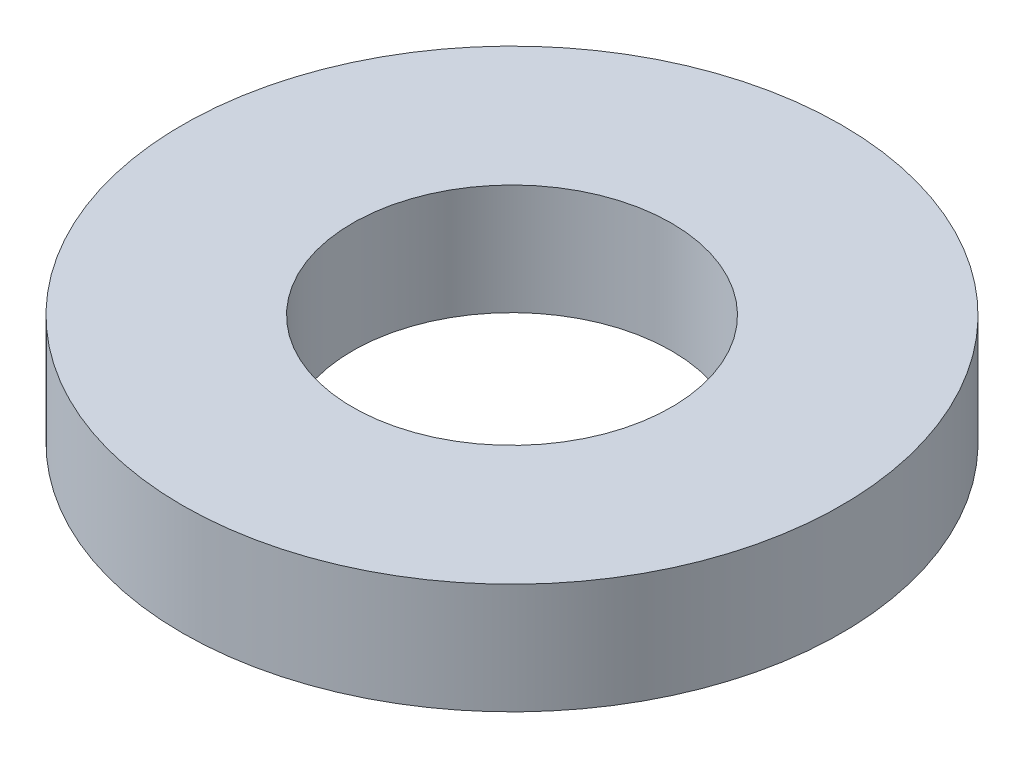
SolidWorks part; units mm, degrees
ref_plane "Front Plane" through (0, 0, 0) normal (0, 0, 1) x (1, 0, 0)
ref_plane "Top Plane" through (0, 0, 0) normal (0, 1, 0) x (1, 0, 0)
ref_plane "Right Plane" through (0, 0, 0) normal (1, 0, 0) x (0, 0, -1)
sketch "Sketch1" plane through (0, 0, 0) normal (0, 1, 0) x (1, 0, 0)
  circle A0 centre (0, 0) radius 77.5
  dimension "FLANGE_OD" = 155
extrude "Boss-Extrude1" add sketch "Sketch1" along normal blind 26
sketch "Sketch2" plane through (0, 0, 0) normal (0, 1, 0) x (1, 0, 0)
  circle A0 centre (0, 0) radius 37.5
  dimension "BORE_D" = 75
extrude "Cut-Extrude1" cut sketch "Sketch2" along normal through all
sketch "Sketch3" plane through (0, 26, 0) normal (0, 1, 0) x (1, 0, 0)
  circle A0 centre (0, 0) radius 28.4626 construction
  circle A1 centre (-28.4626, 0) radius 2.5612
  dimension "BOLT_D" = 5.1223
  dimension "BOLT_PCD" = 56.9252
extrude "Cut-Extrude2" cut sketch "Sketch3" against normal blind 21.7469 rebuild error yes
pattern_circular "CirPattern1" count 4 over 360 rebuild error yes
